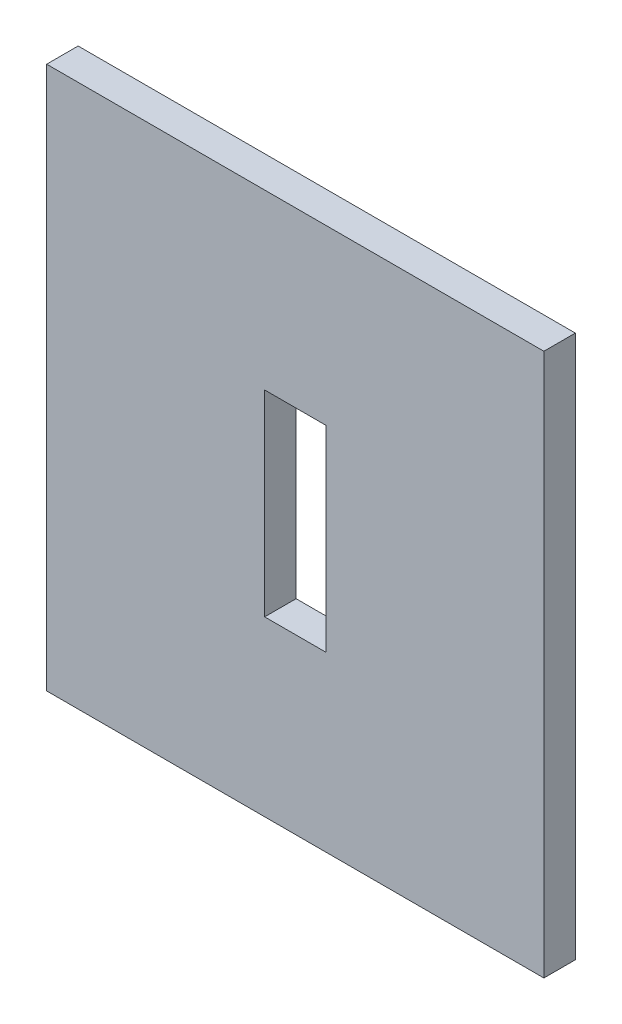
SolidWorks part; units mm, degrees
material "Maple"
ref_plane "Front Plane" through (0, 0, 0) normal (0, 0, 1) x (1, 0, 0)
ref_plane "Top Plane" through (0, 0, 0) normal (0, 1, 0) x (1, 0, 0)
ref_plane "Right Plane" through (0, 0, 0) normal (1, 0, 0) x (0, 0, -1)
sketch "Sketch1" plane through (0, 0, 0) normal (0, 0, 1) x (1, 0, 0)
  line L1 (-25.085, 27.385) -> (25.085, 27.385)
  line L2 (-25.085, 27.385) -> (-25.085, -27.385)
  line L3 (-25.085, -27.385) -> (25.085, -27.385)
  line L4 (25.085, 27.385) -> (25.085, -27.385)
  line L5 (-25.085, 27.385) -> (25.085, -27.385) construction
  line L6 (-25.085, -27.385) -> (25.085, 27.385) construction
  point P1 (0, 0)
  dimension "D1" = 50.17
  dimension "D2" = 54.77
extrude "Boss-Extrude1" add sketch "Sketch1" along normal blind 3.175
sketch "Sketch3" plane through (0, 0, 3.175) normal (0, 0, 1) x (1, 0, 0)
  line L1 (-3.09, 9.915) -> (3.09, 9.915)
  line L2 (-3.09, 9.915) -> (-3.09, -9.915)
  line L3 (-3.09, -9.915) -> (3.09, -9.915)
  line L4 (3.09, 9.915) -> (3.09, -9.915)
  line L5 (-3.09, 9.915) -> (3.09, -9.915) construction
  line L6 (-3.09, -9.915) -> (3.09, 9.915) construction
  point P0 (0, 0)
  dimension "D1" = 19.83
  dimension "D2" = 6.18
extrude "Cut-Extrude1" cut sketch "Sketch3" against normal through all
sketch "Sketch4" plane through (0, 0, 0) normal (1, 0, 0) x (0, 0, -1)
  line L0 (-1.5875, 27.385) -> (-1.5875, -27.385) construction
  line L1 (-3.175, 27.385) -> (0, 27.385) construction
  line L2 (-3.175, -27.385) -> (0, -27.385) construction
ref_axis "Axis1" through (0, 27.385, 1.5875) along (0, -1, 0)
equation "\"length\"=50"
equation "\"D1@Sketch1\"=\"length\" + 2*\"kerf\""
equation "\"width\"=54.6"
equation "\"D2@Sketch1\"=\"width\" + 2*\"kerf\""
equation "\"depth\"=3.175"
equation "\"D1@Boss-Extrude1\"=\"depth\""
equation "\"width2\"=20"
equation "\"D1@Sketch3\"=\"width2\" - 2*\"kerf\""
equation "\"dist\"=3.175"
equation "\"kerf\"= 0.17 / 2"
equation "\"D2@Sketch3\"=6.35 - 2*\"kerf\""
